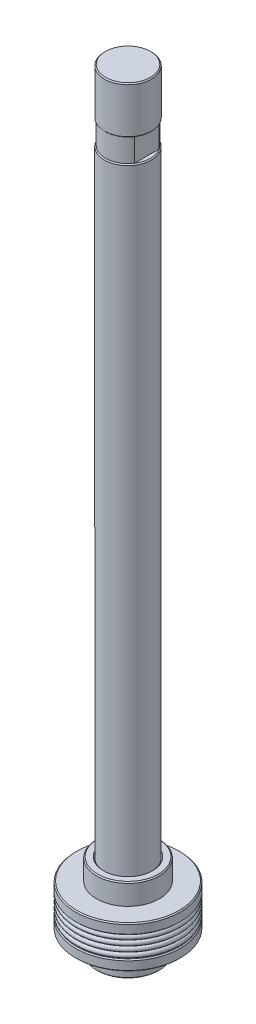
SolidWorks part; units mm, degrees
ref_plane "前基準面" through (0, 0, 0) normal (0, 0, 1) x (1, 0, 0)
ref_plane "上基準面" through (0, 0, 0) normal (0, 1, 0) x (1, 0, 0)
ref_plane "右基準面" through (0, 0, 0) normal (1, 0, 0) x (0, 0, -1)
sketch "草圖1" plane through (0, 0, 0) normal (0, 1, 0) x (1, 0, 0)
  circle A0 centre (0, 0) radius 22.5
  dimension "D1" = 45
extrude "填料-伸長1" add sketch "草圖1" along normal blind 736
sketch "草圖2" plane through (0, 0, 0) normal (0, 0, 1) x (1, 0, 0)
  line L0 (22.5, 691) -> (22.5, 669)
  line L1 (22.5, 0) -> (22.5, 736) construction
  line L2 (22.5, 669) -> (21.5, 669)
  line L3 (21.5, 669) -> (21.5, 691)
  line L4 (21.5, 691) -> (22.5, 691)
  line L6 (0, -264) -> (0, 49736) construction
  line L7 (22.5, 736) -> (-22.5, 736) construction
  point P13 (0, 736)
  dimension "D1" = 43
  dimension "D2" = 45
  dimension "D3" = 22
revolve "除料-旋轉1" cut sketch "草圖2" angle 360 about L6
sketch "草圖3" plane through (0, 0, 0) normal (0, 0, 1) x (1, 0, 0)
  line L0 (22.5, 669) -> (-22.5, 669) construction
  line L1 (-22.5, 691) -> (-18, 691)
  line L2 (-22.5, 691) -> (-22.5, 669)
  line L3 (-22.5, 669) -> (-18, 669)
  line L4 (-18, 691) -> (-18, 669)
  line L5 (0, -1000) -> (0, 49000) construction
  line L6 (22.5, 691) -> (18, 691)
  line L7 (22.5, 691) -> (22.5, 669)
  line L8 (22.5, 669) -> (18, 669)
  line L9 (18, 691) -> (18, 669)
  dimension "D1" = 36
extrude "除料-伸長1" cut sketch "草圖3" against normal mid plane 736
chamfer "導角1" distance 1 angle 45 2 edges at (22.5, 669, 0) (22.5, 691, 0)
chamfer "導角2" distance 1 angle 45 1 edges at (0, 736, 22.5)
chamfer "導角3" distance 1 angle 45 1 edges at (0, 0, 22.5)
sketch "草圖4" plane through (0, 0, 0) normal (0, 0, 1) x (1, 0, 0)
  line L0 (0, -1000) -> (0, 49000) construction
  line L1 (-21.5, 0) -> (21.5, 0) construction
  line L2 (-22.5, 80) -> (-22.5, 0)
  line L3 (-22.5, 668) -> (-22.5, 1) construction
  line L4 (-22.5, 0) -> (-30, 0)
  line L5 (-30, 0) -> (-30, 20)
  line L6 (-30, 20) -> (-50, 20)
  line L7 (-50, 20) -> (-50, 60)
  line L8 (-50, 60) -> (-30, 60)
  line L9 (-30, 60) -> (-30, 80)
  line L10 (-30, 80) -> (-22.5, 80)
  point P5 (0, 0)
  dimension "D1" = 20
  dimension "D2" = 40
  dimension "D3" = 20
  dimension "D4" = 60
  dimension "D5" = 100
  dimension "D6" = 60
revolve "旋轉1" add sketch "草圖4" angle 360 about L0
sketch "草圖5" plane through (0, 0, 0) normal (0, 0, 1) x (1, 0, 0)
  line L0 (-50, 60) -> (-50, 20) construction
  line L1 (-50, 50) -> (-45, 50)
  line L2 (-50, 50) -> (-50, 30)
  line L3 (-50, 30) -> (-45, 30)
  line L4 (-45, 50) -> (-45, 30)
  line L5 (-950, 40) -> (49050, 40) construction
  line L6 (50, 20) -> (50, 60) construction
  line L7 (0, -1000) -> (0, 49000) construction
  line L8 (50, 60) -> (-50, 60) construction
  point P11 (50, 40)
  dimension "D1" = 5
  dimension "D2" = 10
revolve "除料-旋轉2" cut sketch "草圖5" angle 360 about L7
sketch "草圖6" plane through (0, 0, 0) normal (0, 0, 1) x (1, 0, 0)
  line L0 (-45, 50) -> (-45, 30) construction
  line L1 (-50, 50) -> (50, 50) construction
  line L2 (-50, 60) -> (-50, 50) construction
  line L3 (0, -1000) -> (0, 49000) construction
  circle A0 centre (-47.5, 47.5) radius 2.5
  circle A1 centre (-47.5, 42.5) radius 2.5
  circle A2 centre (-47.5, 37.5) radius 2.5
  circle A3 centre (-47.5, 32.5) radius 2.5
  dimension "D1" = 4
revolve "旋轉2" add sketch "草圖6" angle 360 about L3
chamfer "導角4" distance 1 angle 45 4 edges at (50, 60, 0) (50, 20, 0) (50, 30, 0) (50, 50, 0)
chamfer "導角5" distance 1 angle 45 2 edges at (22.5, 80, 0) (22.5, 0, 0)
chamfer "導角6" distance 1 angle 45 2 edges at (30, 80, 0) (30, 0, 0)
ref_plane "平面1" through (0, 0, 50) normal (0, 0, 1) x (1, 0, 0)
hole_wizard "M12x1.5 螺紋孔1" positions "草圖10" profile "草圖9" tap size "M12x1.5" standard "ISO"
sketch "草圖10" plane through (0, 0, 50) normal (0, 0, 1) x (1, 0, 0)
  line L0 (0, 668) -> (0, 1) construction
  line L1 (-29, 0) -> (29, 0) construction
  point P0 (0, 10)
  dimension "D1" = 10
sketch "草圖9" plane through (0, 10, 50) normal (1, 0, 0) x (0, -1, 0)
  line L0 (0, 0) -> (0, 53.1545)
  line L1 (0, 53.1545) -> (5.25, 50)
  line L2 (5.25, 50) -> (5.25, 0)
  line L5 (5.25, 0) -> (0, 0)
  line L10 (0, 53.1545) -> (-5.25, 50) construction
  line L11 (0, -6.35) -> (0, 107.95) construction
  dimension "螺孔鑽直徑" = 10.5
  dimension "螺孔鑽深度" = 50
  dimension "導頭角度" = 118
cosmetic thread "鑽孔螺紋1" parameters "D1"=45, "D2"=12
